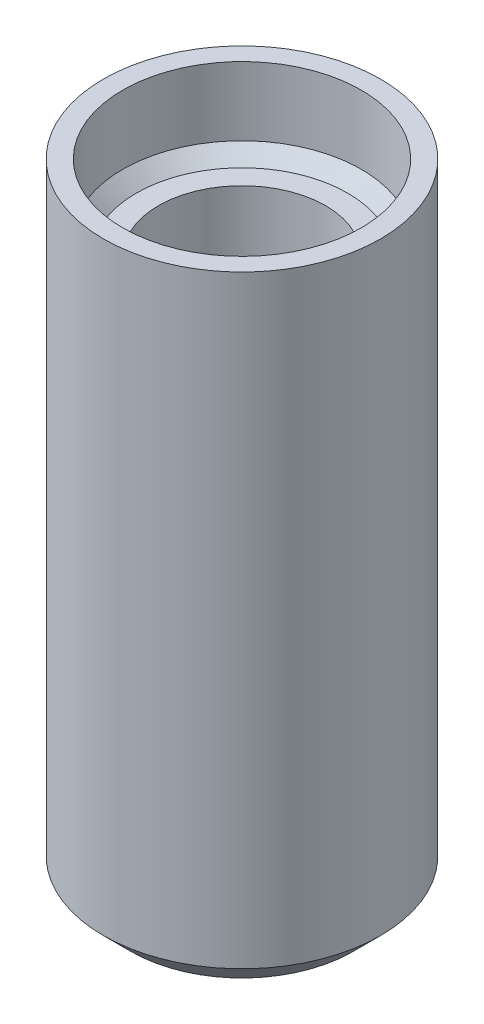
SolidWorks part; units mm, degrees
ref_plane "Front Plane" through (0, 0, 0) normal (0, 0, 1) x (1, 0, 0)
ref_plane "Top Plane" through (0, 0, 0) normal (0, 1, 0) x (1, 0, 0)
ref_plane "Right Plane" through (0, 0, 0) normal (1, 0, 0) x (0, 0, -1)
sketch "Sketch1" plane through (0, 0, 0) normal (0, 1, 0) x (1, 0, 0)
  line L0 (-2.5652, -1.65) -> (2.5652, -1.65)
  circle A0 centre (0, 0) radius 3.05
  circle A1 centre (0, 0) radius 5.05
  dimension "D1" = 6.1
  dimension "D3" = 1.65
  dimension "D2" = 2
extrude "Boss-Extrude1" add sketch "Sketch1" along normal blind 20 contours A1 A0 | L0 A0 region at (0, 0, 2.2227) region at (-4.9072, 0, 0)
sketch "Sketch2" plane through (0, 0, 0) normal (0, -1, 0) x (1, 0, 0)
  circle A1 centre (0, 0) radius 5.05
  circle A2 centre (0, 0) radius 5.05
  dimension "D1" = 0
extrude "Boss-Extrude2" add sketch "Sketch2" against normal blind 2
sketch "Sketch4" plane through (0, 20, 0) normal (0, 1, 0) x (1, 0, 0)
  circle A0 centre (0, 0) radius 4.35
  circle A1 centre (0, 0) radius 5.05
  circle A2 centre (0, 0) radius 5.05
  dimension "D1" = 0
  dimension "D2" = 0.7
extrude "Boss-Extrude3" add sketch "Sketch4" along normal blind 3
chamfer "Chamfer1" distance 1 angle 45 1 edges at (0, 0, 5.05)
chamfer "Chamfer2" distance 0.5 angle 45 1 edges at (0, 20, 4.35)
sketch "Sketch5" plane through (0, 0, 0) normal (0, -1, 0) x (1, 0, 0)
  line L0 (-1.326, 0) -> (1.326, 0) construction
  line L1 (-3.5217, -2) -> (3.5217, -2) construction
  circle A0 centre (0, 0) radius 4.05 construction
  text T0 "<b>4</b>" font "Calibri" height in points 16
  dimension "D1" = 2
extrude "Cut-Extrude1" cut sketch "Sketch5" against normal blind 0.4
extrude "Boss-Extrude4" add sketch "Sketch5<2>" against normal blind 0.4 separate body
sketch "Sketch5<2>" plane through (0, 0, 0) normal (0, -1, 0) x (1, 0, 0) same geometry as "Sketch5"
equation "\"ID\"= 6.3"
equation "\"notch\"= 6.3 / 2 - 1.5"
equation "\"D3@Sketch1\"=\"notch\""
